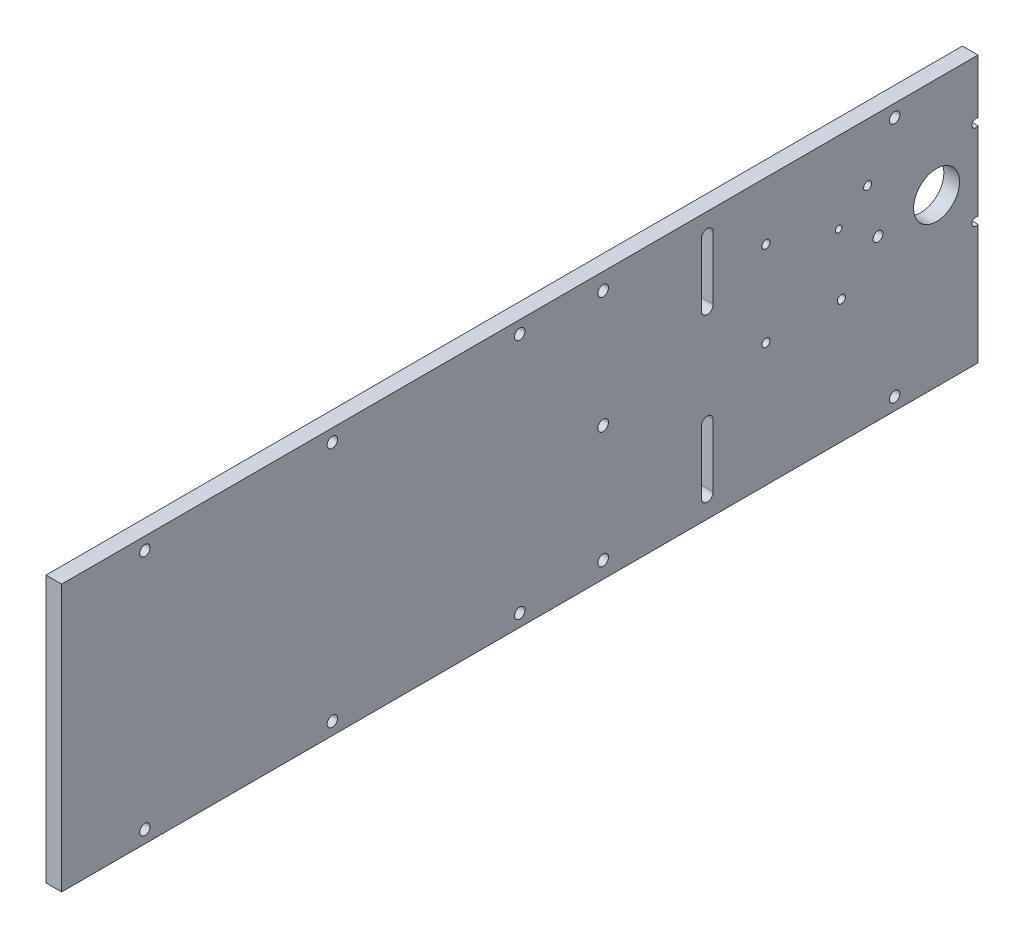
SolidWorks part; units mm, degrees
material "6061-T6 (SS)"
ref_plane "Front Plane" through (0, 0, 0) normal (0, 0, 1) x (1, 0, 0)
ref_plane "Top Plane" through (0, 0, 0) normal (0, 1, 0) x (1, 0, 0)
ref_plane "Right Plane" through (0, 0, 0) normal (1, 0, 0) x (0, 0, -1)
sketch "Sketch1" plane through (0, 0, 0) normal (1, 0, 0) x (0, 0, -1)
  line L0 (0, 12.7) -> (0, -12.7) construction
  line L1 (0, -12.7) -> (33.2976, -40.64) construction
  line L2 (33.2976, -40.64) -> (312.6976, -40.64)
  line L3 (312.6976, -40.64) -> (345.9952, -12.7) construction
  line L4 (345.9952, -12.7) -> (345.9952, 12.7) construction
  line L5 (345.9952, 12.7) -> (312.6976, 40.64) construction
  line L6 (312.6976, 40.64) -> (33.2976, 40.64)
  line L7 (33.2976, 40.64) -> (0, 12.7) construction
  line L8 (33.2976, 40.64) -> (33.2976, -40.64)
  line L9 (312.6976, 40.64) -> (312.6976, -40.64)
  line L10 (0, 0) -> (345.9952, 0) construction
  line L11 (0, 12.7) -> (-63.5681, -40.64) construction
  line L12 (-63.5681, -40.64) -> (33.2976, -40.64) construction
  line L13 (312.6976, 40.64) -> (409.5633, 40.64) construction
  line L14 (409.5633, 40.64) -> (345.9952, -12.7) construction
  point P10 (33.2976, 0)
  point P12 (312.6976, 0)
  dimension "D1" = 81.28
  dimension "D2" = 279.4
  dimension "D3" = 25.4
  dimension "D4" = 40
extrude "Boss-Extrude1" add sketch "Sketch1" along normal blind 4.7625
sketch "Sketch2" plane through (4.7625, 0, 0) normal (1, 0, 0) x (0, 0, -1)
  line L0 (-3.2177, 10) -> (373.048, 10) construction
  line L1 (312.6976, -40.64) -> (409.5633, 40.64) construction
  line L2 (345.048, 10) -> (245.048, 10) construction
  line L3 (245.048, -5) -> (345.048, -5) construction
  line L4 (245.048, -5) -> (245.048, 25) construction
  line L5 (245.048, 25) -> (345.048, 25) construction
  line L6 (345.048, -5) -> (345.048, 25) construction
  line L7 (0, 0) -> (361.1305, 0) construction
  line L9 (33.2976, 40.64) -> (-63.5681, -40.64) construction
  circle A0 centre (300.048, 10) radius 6.9977
  circle A1 centre (282.2147, 8) radius 1.4986
  circle A2 centre (270.2178, 15.9334) radius 0.9906
  circle A3 centre (282.2147, 8) radius 11.4777 construction
  circle A4 centre (270.2178, 15.9334) radius 7.1501 construction
  circle A5 centre (300.048, 10) radius 12.827 construction
  circle A6 centre (261.048, 10) radius 14 construction
  circle A7 centre (282.2147, 8) radius 5.1181 construction
  circle A8 centre (331.0042, 10) radius 4.7625
  point P11 (300.048, 10)
  point P12 (282.2147, 8)
  point P13 (270.2178, 15.9334)
  point P23 (261.048, 10)
  dimension "D5" = 13.9954
  dimension "D6" = 2.9972
  dimension "D7" = 1.9812
  dimension "D8" = 25.654
  dimension "D9" = 22.9553
  dimension "D10" = 14.3002
  dimension "D12" = 28
  dimension "D13" = 10.2362
  dimension "D17" = 9.525
  dimension "D1" = 17.9451
  dimension "D2" = 14.3828
  dimension "D3" = 30
  dimension "D4" = 100
  dimension "D11" = 10.922
  dimension "D14" = 16
  dimension "D15" = 13
  dimension "D16" = 55
  dimension "D18" = 30.9562
  dimension "D19" = 28
  dimension "D20" = 10
extrude "Gearbox (with Press fits)" cut sketch "Sketch2" against normal through all
sketch "Sketch6" plane through (4.7625, 0, 0) normal (1, 0, 0) x (0, 0, -1)
  line L0 (0, 0) -> (361.1305, 0) construction
  line L1 (230.1476, 36.83) -> (230.1476, -36.83) construction
  line L2 (28.757, 36.83) -> (405.0227, 36.83) construction
  line L3 (33.2976, 40.64) -> (-63.5681, -40.64) construction
  line L4 (230.1476, 34.29) -> (230.1476, 15.24) construction
  line L5 (312.6976, 40.64) -> (33.2976, 40.64) construction
  line L6 (312.6976, -40.64) -> (409.5633, 40.64) construction
  line L7 (231.9764, 34.29) -> (231.9764, 15.24)
  line L8 (228.3188, 34.29) -> (228.3188, 15.24)
  line L9 (409.5633, 40.64) -> (33.2976, 40.64) construction
  line L10 (230.1476, -34.29) -> (230.1476, -15.24) construction
  line L11 (231.9764, -34.29) -> (231.9764, -15.24)
  line L12 (228.3188, -34.29) -> (228.3188, -15.24)
  circle A0 centre (287.2976, 36.83) radius 1.5939
  circle A1 centre (230.1476, 36.83) radius 1.5939 construction
  circle A2 centre (172.9976, 36.83) radius 1.5939
  circle A3 centre (115.8476, 36.83) radius 1.5938
  circle A4 centre (58.6976, 36.83) radius 1.5938
  circle A5 centre (58.6976, -36.83) radius 1.5938
  circle A6 centre (115.8476, -36.83) radius 1.5938
  circle A7 centre (172.9976, -36.83) radius 1.5939
  circle A8 centre (230.1476, -36.83) radius 1.5939 construction
  circle A9 centre (287.2976, -36.83) radius 1.5939
  arc A10 (231.9764, 34.29) -> (228.3188, 34.29) centre (230.1476, 34.29) ccw
  arc A11 (228.3188, 15.24) -> (231.9764, 15.24) centre (230.1476, 15.24) ccw
  arc A12 (231.9764, -34.29) -> (228.3188, -34.29) centre (230.1476, -34.29) cw
  arc A13 (228.3188, -15.24) -> (231.9764, -15.24) centre (230.1476, -15.24) cw
  point P9 (230.1476, 24.765)
  point P43 (230.1476, -24.765)
  dimension "D2" = 3.1877
  dimension "D1" = 3.81
  dimension "D3" = 25.4
  dimension "D5" = 3.6576
  dimension "D6" = 6.35
  dimension "D7" = 19.05
  dimension "D4" = 5
extrude "Cut-Extrude2" cut sketch "Sketch6" against normal through all
hole_wizard "#4 Clearance Hole2" positions "Sketch8" profile "Sketch7" hole size "#4" standard "ANSI Inch" end condition through all
sketch "Sketch8" plane through (4.7625, 0, 0) normal (1, 0, 0) x (0, 0, -1)
  line L0 (0, 0) -> (361.1305, 0) construction
  line L1 (312.6976, -40.64) -> (409.5633, 40.64) construction
  line L3 (27.2435, 35.56) -> (403.5092, 35.56) construction
  line L4 (33.2976, 40.64) -> (-63.5681, -40.64) construction
  line L7 (198.3976, 35.56) -> (198.3976, -35.56) construction
  line L8 (409.5633, 40.64) -> (33.2976, 40.64) construction
  point P15 (198.3976, 35.56)
  point P18 (198.3976, -35.56)
  point P30 (198.3976, 0)
  dimension "D2" = 165.1
  dimension "D3" = 5.08
sketch "Sketch7" plane through (4.7625, 35.56, -198.3976) normal (0, 1, 0) x (0, 0, -1)
  line L0 (0, 0) -> (0, 4.7625)
  line L1 (0, 4.7625) -> (1.6319, 4.7625)
  line L2 (1.6319, 4.7625) -> (1.6319, 0)
  line L5 (1.6319, 0) -> (0, 0)
  line L11 (0, -6.35) -> (0, 107.95) construction
  dimension "Thru Hole Dia." = 3.2639
  dimension "Thru Hole Depth" = 4.7625
hole_wizard "#2 Clearance Hole1" positions "Sketch10" profile "Sketch9" hole size "#2" standard "ANSI Inch"
sketch "Sketch10" plane through (4.7625, 0, 0) normal (1, 0, 0) x (0, 0, -1)
  line L0 (245.048, 40.64) -> (245.048, -40.64) construction
  line L1 (409.5633, 40.64) -> (33.2976, 40.64) construction
  line L2 (-63.5681, -40.64) -> (312.6976, -40.64) construction
  line L4 (248.048, 40.64) -> (248.048, -40.64) construction
  line L6 (245.048, 23) -> (335.048, 23) construction
  line L8 (245.048, -6) -> (328.5196, -6) construction
  line L10 (245.048, -3) -> (335.048, -3) construction
  line L11 (312.048, 23) -> (312.048, -3) construction
  line L12 (373.048, 10) -> (261.048, 10) construction
  line L13 (312.6976, -40.64) -> (409.5633, 40.64) construction
  line L14 (331.0042, 10) -> (331.0042, 40.64) construction
  line L15 (335.048, 23) -> (335.048, -3) construction
  circle A0 centre (331.0042, 10) radius 4.7625 construction
  point P25 (248.048, -3)
  point P27 (248.048, 23)
  point P29 (271.048, -3)
  point P31 (312.048, -3)
  point P33 (279.048, 23)
  point P35 (312.048, 23)
  point P70 (335.048, 23)
  point P72 (335.048, -3)
  dimension "D1" = 3
  dimension "D2" = 3
  dimension "D3" = 26
  dimension "D4" = 34
  dimension "D5" = 67
  dimension "D6" = 29
  dimension "D7" = 69.9562
  dimension "D8" = 16
  dimension "D9" = 16
  dimension "D10" = 90
sketch "Sketch9" plane through (4.7625, -3, -248.048) normal (0, 1, 0) x (0, 0, -1)
  line L0 (0, 0) -> (0, 5.5586)
  line L1 (0, 5.5586) -> (1.2192, 4.826)
  line L2 (1.2192, 4.826) -> (1.2192, 0)
  line L5 (1.2192, 0) -> (0, 0)
  line L10 (0, 5.5586) -> (-1.2192, 4.826) construction
  line L11 (0, -6.35) -> (0, 107.95) construction
  dimension "Hole Dia." = 2.4384
  dimension "Hole Depth" = 4.826
  dimension "Drill Angle" = 118
hole_wizard "#4 Clearance Hole1" positions "Sketch12" profile "Sketch11" hole size "#4" standard "ANSI Inch" rebuild error yes
sketch "Sketch12" plane through (4.7625, 0, 0) normal (1, 0, 0) x (0, 0, -1)
  line L9 (-15.1353, 0) -> (361.1305, 0) construction
  line L10 (33.2976, 40.64) -> (-63.5681, -40.64) construction
  line L11 (312.6976, -40.64) -> (409.5633, 40.64) construction
  line L13 (403.636, 40.64) -> (306.7703, -40.64) construction
  line L14 (409.5633, 40.64) -> (33.2976, 40.64) construction
  line L15 (-63.5681, -40.64) -> (312.6976, -40.64) construction
  line L17 (39.2249, 40.64) -> (-57.6408, -40.64) construction
  line L18 (355.2032, 0) -> (-9.208, 0) construction
  line L19 (-36.4485, -22.8575) -> (327.9626, -22.8575) construction
  line L21 (-21.8554, -10.6124) -> (342.5558, -10.6124) construction
  line L23 (3.4394, 10.6124) -> (367.8505, 10.6124) construction
  line L25 (18.0326, 22.8575) -> (382.4437, 22.8575) construction
  point P40 (327.9626, -22.8575)
  point P42 (342.5558, -10.6124)
  point P44 (367.8505, 10.6124)
  point P46 (382.4437, 22.8575)
  point P54 (-36.4485, -22.8575)
  point P56 (-21.8554, -10.6124)
  point P58 (3.4394, 10.6124)
  point P60 (18.0326, 22.8575)
  dimension "D1" = 16.51
  dimension "D2" = 19.05
  dimension "D3" = 16.51
  dimension "D4" = 19.05
  dimension "D5" = 3.81
  dimension "D6" = 3.81
sketch "Sketch11" plane through (4.7625, -22.8575, -327.9626) normal (0, 1, 0) x (0, 0, -1)
  line L0 (0, 0) -> (0, 5.8066)
  line L1 (0, 5.8066) -> (1.6319, 4.826)
  line L2 (1.6319, 4.826) -> (1.6319, 0)
  line L5 (1.6319, 0) -> (0, 0)
  line L10 (0, 5.8066) -> (-1.6319, 4.826) construction
  line L11 (0, -6.35) -> (0, 107.95) construction
  dimension "Hole Dia." = 3.2639
  dimension "Hole Depth" = 4.826
  dimension "Drill Angle" = 118
sketch "Sketch15" plane through (4.7625, 0, 0) normal (1, 0, 0) x (0, 0, -1)
  line L0 (217.2296, 27.94) -> (238.523, 27.94)
  line L1 (210.725, 16.7148) -> (232.0185, -23.2727)
  line L2 (204.7476, -24.765) -> (204.7476, 15.2225)
  line L3 (-28.6752, -27.94) -> (37.92, 27.94) construction
  line L4 (214.4271, 23.2727) -> (235.7206, -16.7148)
  line L5 (241.698, 24.765) -> (241.698, -15.2225)
  line L6 (229.216, -27.94) -> (207.9226, -27.94)
  line L7 (-48.4329, -27.94) -> (327.8329, -27.94) construction
  line L8 (33.2976, 40.64) -> (-63.5681, -40.64) construction
  line L9 (312.6976, -40.64) -> (409.5633, 40.64) construction
  line L10 (-63.5681, -40.64) -> (312.6976, -40.64) construction
  line L11 (18.1623, 27.94) -> (394.4281, 27.94) construction
  line L12 (409.5633, 40.64) -> (33.2976, 40.64) construction
  line L13 (35.7449, 26.1148) -> (-21.9928, -22.3328)
  line L14 (-19.9519, -27.94) -> (88.637, -27.94)
  line L15 (90.8271, -22.4663) -> (39.9758, 25.9814)
  line L16 (62.0768, 22.4663) -> (112.7937, -25.8534)
  line L17 (117.1739, -25.8534) -> (167.8909, 22.4663)
  line L18 (64.2668, 27.94) -> (165.7008, 27.94)
  line L19 (139.1405, -22.4663) -> (186.6825, 22.8285)
  line L20 (192.0476, 20.5298) -> (192.0476, -24.765)
  line L21 (188.8726, -27.94) -> (141.3306, -27.94)
  line L22 (114.9838, 27.94) -> (114.9838, -27.94) construction
  line L23 (254.398, 27.94) -> (254.398, -27.94) construction
  line L24 (254.398, -12.525) -> (254.398, -24.765)
  line L25 (257.573, -27.94) -> (306.9196, -27.94)
  line L26 (308.9604, -27.1972) -> (323.5475, -14.9572)
  line L27 (321.5066, -9.35) -> (257.573, -9.35)
  circle A0 centre (198.3976, 0) radius 6.35 construction
  circle A1 centre (198.3976, 35.56) radius 6.35 construction
  circle A2 centre (198.3976, -35.56) radius 6.35 construction
  circle A3 centre (248.048, -3) radius 6.35 construction
  arc A4 (204.7476, -24.765) -> (207.9226, -27.94) centre (207.9226, -24.765) ccw
  arc A5 (229.216, -27.94) -> (232.0185, -23.2727) centre (229.216, -24.765) ccw
  arc A6 (241.698, -15.2225) -> (235.7206, -16.7148) centre (238.523, -15.2225) cw
  arc A7 (238.523, 27.94) -> (241.698, 24.765) centre (238.523, 24.765) cw
  arc A8 (217.2296, 27.94) -> (214.4271, 23.2727) centre (217.2296, 24.765) ccw
  arc A9 (204.7476, 15.2225) -> (210.725, 16.7148) centre (207.9226, 15.2225) cw
  arc A10 (-21.9928, -22.3328) -> (-19.9519, -27.94) centre (-19.9519, -24.765) ccw
  arc A11 (186.6825, 22.8285) -> (192.0476, 20.5298) centre (188.8726, 20.5298) cw
  arc A12 (192.0476, -24.765) -> (188.8726, -27.94) centre (188.8726, -24.765) cw
  arc A13 (139.1405, -22.4663) -> (141.3306, -27.94) centre (141.3306, -24.765) ccw
  arc A14 (88.637, -27.94) -> (90.8271, -22.4663) centre (88.637, -24.765) ccw
  arc A15 (35.7449, 26.1148) -> (39.9758, 25.9814) centre (37.7857, 23.6826) cw
  arc A16 (112.7937, -25.8534) -> (117.1739, -25.8534) centre (114.9838, -23.5547) ccw
  arc A17 (167.8909, 22.4663) -> (165.7008, 27.94) centre (165.7008, 24.765) ccw
  arc A18 (62.0768, 22.4663) -> (64.2668, 27.94) centre (64.2668, 24.765) cw
  circle A19 centre (271.048, -3) radius 6.35 construction
  arc A20 (323.5475, -14.9572) -> (321.5066, -9.35) centre (321.5066, -12.525) ccw
  arc A21 (306.9196, -27.94) -> (308.9604, -27.1972) centre (306.9196, -24.765) ccw
  arc A22 (254.398, -24.765) -> (257.573, -27.94) centre (257.573, -24.765) ccw
  arc A23 (254.398, -12.525) -> (257.573, -9.35) centre (257.573, -12.525) cw
  point P15 (204.7476, -27.94)
  point P36 (241.698, -27.94)
  point P40 (204.7476, -27.94)
  point P59 (192.0476, 27.94)
  point P62 (192.0476, -27.94)
  point P65 (133.3952, -27.94)
  point P68 (96.5724, -27.94)
  point P77 (173.6362, 27.94)
  point P80 (56.3315, 27.94)
  point P82 (204.7476, 27.94)
  point P95 (308.0752, -27.94)
  point P101 (254.398, -9.35)
  dimension "D1" = 12.7
  dimension "D2" = 12.7
  dimension "D3" = 12.7
  dimension "D4" = 12.7
  dimension "D8" = 3.175
  dimension "D12" = 3.175
  dimension "D13" = 12.7
  dimension "D15" = 3.175
  dimension "D5" = 12.7
  dimension "D6" = 12.7
  dimension "D7" = 6.35
  dimension "D9" = 12.7
  dimension "D10" = 12.7
  dimension "D11" = 12.7
  dimension "D14" = 12.7
extrude "Cut-Extrude3" [suppressed] cut sketch "Sketch15" against normal through all
